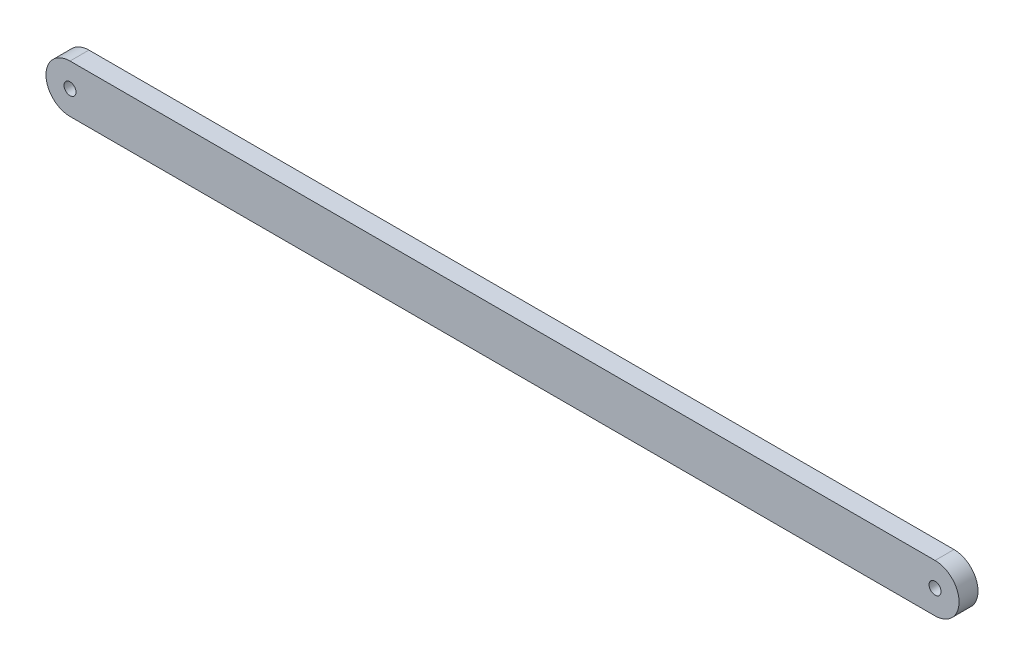
SolidWorks part; units mm, degrees
ref_plane "Front Plane" through (0, 0, 0) normal (0, 0, 1) x (1, 0, 0)
ref_plane "Top Plane" through (0, 0, 0) normal (0, 1, 0) x (1, 0, 0)
ref_plane "Right Plane" through (0, 0, 0) normal (1, 0, 0) x (0, 0, -1)
sketch "Sketch1" plane through (0, 0, 0) normal (0, 0, 1) x (1, 0, 0)
  line L0 (0, 12.7) -> (457.2, 12.7)
  line L1 (0, -12.7) -> (457.2, -12.7)
  arc A0 (0, 12.7) -> (0, -12.7) centre (0, 0) ccw
  arc A1 (457.2, -12.7) -> (457.2, 12.7) centre (457.2, 0) ccw
  circle A2 centre (0, 0) radius 3.175
  circle A3 centre (457.2, 0) radius 3.175
  dimension "D1" = 25.4
  dimension "D3" = 6.35
  dimension "D2" = 457.2
extrude "Boss-Extrude1" add sketch "Sketch1" along normal blind 10
